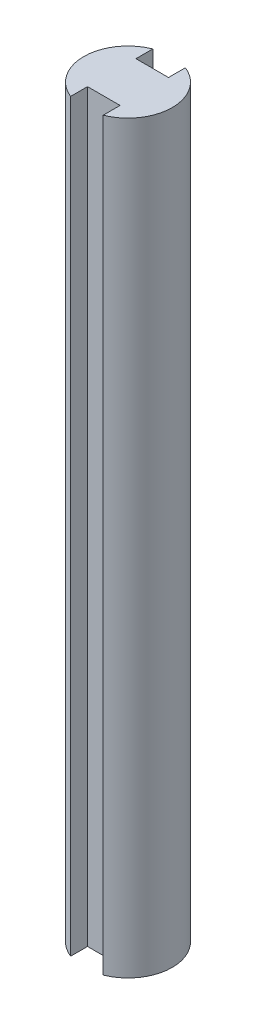
SolidWorks part; units mm, degrees
material "PVC Rigid"
ref_plane "Front Plane" through (0, 0, 0) normal (0, 0, 1) x (1, 0, 0)
ref_plane "Top Plane" through (0, 0, 0) normal (0, 1, 0) x (1, 0, 0)
ref_plane "Right Plane" through (0, 0, 0) normal (1, 0, 0) x (0, 0, -1)
sketch "Sketch1" plane through (0, 0, 0) normal (0, 1, 0) x (1, 0, 0)
  line L0 (-1.75, 4.4159) -> (-1.75, 2.6)
  line L1 (-1.75, 2.6) -> (1.75, 2.6)
  line L2 (1.75, 2.6) -> (1.75, 4.4159)
  line L3 (-1.75, -4.4159) -> (-1.75, -2.6)
  line L4 (-1.75, -2.6) -> (1.75, -2.6)
  line L5 (1.75, -2.6) -> (1.75, -4.4159)
  circle A0 centre (0, 0) radius 4.75
  dimension "D1" = 9.5
  dimension "D2" = 3.5
  dimension "D3" = 5.2
extrude "Boss-Extrude1" add sketch "Sketch1" along normal blind 80 contours L5 A0 L2 L1 L0 L3 L4 region at (0, 0, 0)
